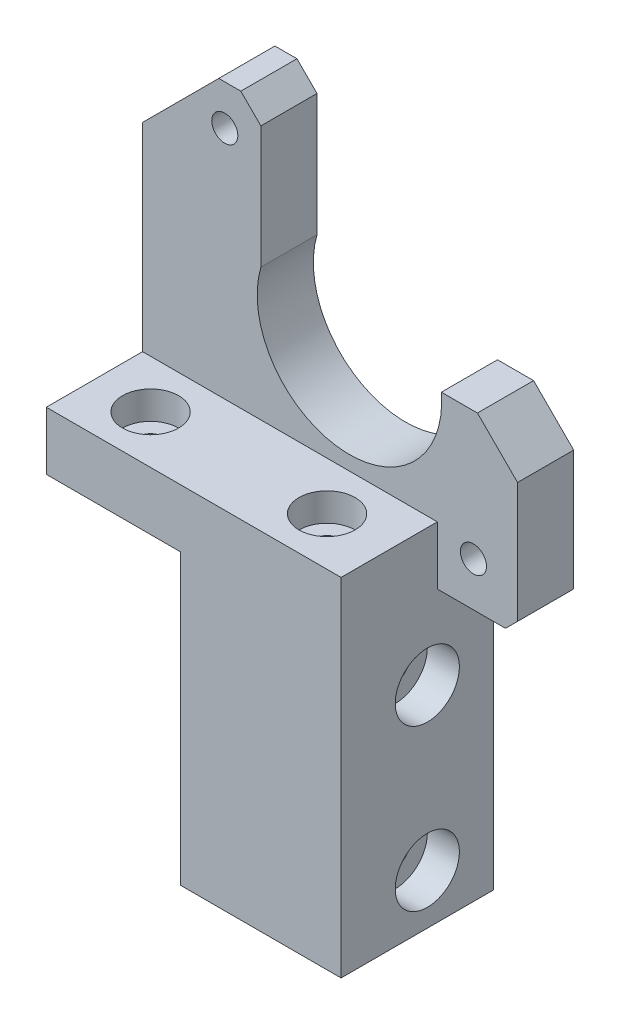
SolidWorks part; units mm, degrees
ref_plane "Front Plane" through (0, 0, 0) normal (0, 0, 1) x (1, 0, 0)
ref_plane "Top Plane" through (0, 0, 0) normal (0, 1, 0) x (1, 0, 0)
ref_plane "Right Plane" through (0, 0, 0) normal (1, 0, 0) x (0, 0, -1)
sketch "Sketch1" plane through (0, 0, 0) normal (0, 0, 1) x (1, 0, 0)
  line L0 (0, 0) -> (20, 0)
  line L1 (20, 0) -> (20, 43.25)
  line L2 (20, 43.25) -> (-16.75, 43.25)
  line L3 (-16.75, 43.25) -> (-16.75, 36)
  line L4 (-16.75, 36) -> (0, 36)
  line L5 (0, 36) -> (0, 0)
  dimension "D1" = 20
  dimension "D2" = 43.25
  dimension "D3" = 16.75
  dimension "D4" = 36
extrude "Boss-Extrude1" add sketch "Sketch1" along normal blind 19
sketch "Sketch2" plane through (0, 0, 0) normal (0, 0, -1) x (-1, 0, 0)
  line L0 (-20, 36) -> (16.75, 36)
  line L1 (16.75, 36) -> (16.75, 68)
  line L2 (16.75, 68) -> (7.25, 77.5)
  line L3 (7.25, 77.5) -> (4.5, 77.5)
  line L4 (4.5, 77.5) -> (2, 75)
  line L5 (2, 75) -> (2, 59.75)
  line L7 (-20, 0) -> (-20, 43.25) construction
  line L8 (-20, 36) -> (-28.5, 36)
  line L9 (-28.5, 36) -> (-30, 37.5)
  line L10 (-30, 37.5) -> (-30, 52.5)
  line L11 (-30, 52.5) -> (-25, 57.5)
  line L12 (-25, 57.5) -> (-20.5, 57.5)
  arc A0 (-20.5, 57.5) -> (2, 59.75) centre (-9.0408, 56.5326) ccw
  point P9 (16.75, 36)
  point P10 (0, 0)
  point P11 (0, 0)
  point P12 (0, 0)
  dimension "D16" = 23
  dimension "D1" = 45
  dimension "D2" = 32
  dimension "D3" = 9.5
  dimension "D4" = 2.75
  dimension "D5" = 45
  dimension "D6" = 2.5
  dimension "D7" = 15.25
  dimension "D9" = 8.5
  dimension "D10" = 135
  dimension "D11" = 1.5
  dimension "D12" = 15
  dimension "D13" = 45
  dimension "D14" = 5
  dimension "D15" = 4.5
extrude "Boss-Extrude2" add sketch "Sketch2" against normal blind 7
sketch "Sketch3" plane through (20, 0, 0) normal (1, 0, 0) x (0, 0, -1)
  line L0 (0, 0) -> (0, 36) construction
  line L1 (-8.25, 26.25) -> (-8.25, 6.25) construction
  line L2 (-19, 0) -> (0, 0) construction
  circle A0 centre (-8.25, 26.25) radius 1.75
  circle A1 centre (-8.25, 6.25) radius 1.75
  dimension "D4" = 3.5
  dimension "D1" = 8.25
  dimension "D2" = 26.25
  dimension "D3" = 6.25
extrude "Cut-Extrude1" cut sketch "Sketch3" against normal through all
sketch "Sketch4" plane through (0, 43.25, 0) normal (0, 1, 0) x (1, 0, 0)
  line L0 (-9.75, -13) -> (12.25, -13) construction
  line L1 (-16.75, -19) -> (-16.75, -7) construction
  line L2 (20, -19) -> (-16.75, -19) construction
  circle A0 centre (-9.75, -13) radius 1.625
  circle A1 centre (12.25, -13) radius 1.625
  dimension "D1" = 3.25
  dimension "D2" = 29
  dimension "D3" = 7
  dimension "D4" = 6
extrude "Cut-Extrude2" cut sketch "Sketch4" against normal blind 7.25
sketch "Sketch5" plane through (0, 43.25, 0) normal (0, 1, 0) x (1, 0, 0)
  circle A0 centre (-9.75, -13) radius 3.5
  circle A1 centre (12.25, -13) radius 3.5
  dimension "D1" = 7
extrude "Cut-Extrude3" cut sketch "Sketch5" against normal blind 3.5
sketch "Sketch6" plane through (20, 0, 0) normal (1, 0, 0) x (0, 0, -1)
  circle A0 centre (-8.25, 26.25) radius 4
  circle A1 centre (-8.25, 6.25) radius 4
  dimension "D1" = 8
extrude "Cut-Extrude4" cut sketch "Sketch6" against normal blind 4
sketch "Sketch7" plane through (0, 0, 0) normal (0, 0, -1) x (-1, 0, 0)
  line L0 (-28.5, 36) -> (-20, 36) construction
  line L1 (-30, 52.5) -> (-30, 37.5) construction
  line L2 (16.75, 36) -> (0, 36) construction
  circle A0 centre (6.5, 72.5) radius 1.625
  circle A1 centre (-24.5, 41.5) radius 1.625
  point P10 (0, 0)
  dimension "D1" = 3.25
  dimension "D2" = 3.25
  dimension "D3" = 5.5
  dimension "D4" = 5.5
  dimension "D5" = 36.5
  dimension "D6" = 36.5
extrude "Cut-Extrude5" cut sketch "Sketch7" against normal through all
